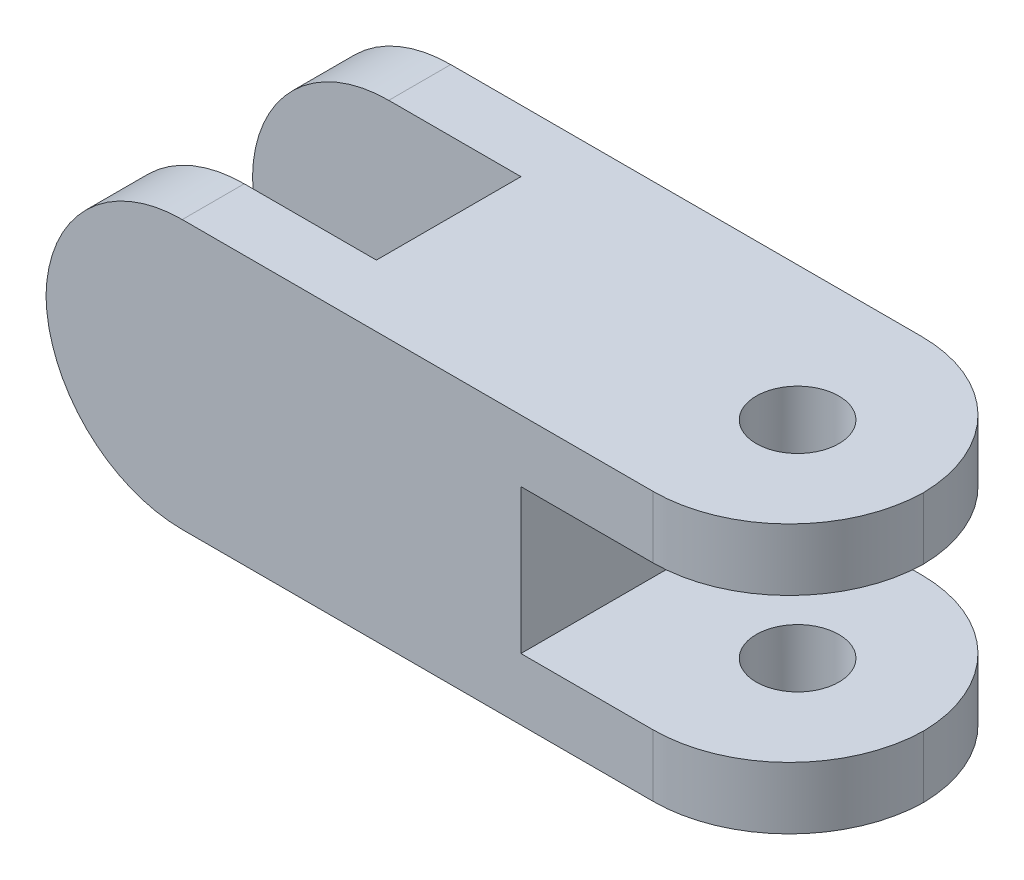
SolidWorks part; units mm, degrees
ref_plane "Plano frontal" through (0, 0, 0) normal (0, 0, 1) x (1, 0, 0)
ref_plane "Plano superior" through (0, 0, 0) normal (0, 1, 0) x (1, 0, 0)
ref_plane "Plano direito" through (0, 0, 0) normal (1, 0, 0) x (0, 0, -1)
sketch "Esboço1" plane through (0, 0, 0) normal (0, 1, 0) x (1, 0, 0)
  line L1 (-90, 32.5) -> (90, 32.5)
  line L2 (-90, 32.5) -> (-90, -32.5)
  line L3 (-90, -32.5) -> (90, -32.5)
  line L4 (90, 32.5) -> (90, -32.5)
  line L5 (-90, 32.5) -> (90, -32.5) construction
  line L6 (-90, -32.5) -> (90, 32.5) construction
  point P0 (0, 0)
  point P6 (0, 0)
  dimension "D1" = 180
  dimension "D2" = 65
extrude "Ressalto-extrusão3" add sketch "Esboço1" along normal mid plane 65
fillet "Filete6" radius 33 2 edges at (90, 0, -32.5) (90, 0, 32.5)
sketch "Esboço5" plane through (0, 0, 32.5) normal (0, 0, 1) x (1, 0, 0)
  line L0 (89.9962, 32.5) -> (89.9962, -32.5) construction
  line L1 (89.9962, 17.5) -> (24.9962, 17.5)
  line L2 (89.9962, 17.5) -> (89.9962, -17.5)
  line L3 (89.9962, -17.5) -> (24.9962, -17.5)
  line L4 (24.9962, 17.5) -> (24.9962, -17.5)
  line L5 (89.9962, 32.5) -> (57, 32.5) construction
  line L6 (57, -32.5) -> (89.9962, -32.5) construction
  dimension "D1" = 15
  dimension "D2" = 15
  dimension "D3" = 65
extrude "Corte-extrusão2" cut sketch "Esboço5" against normal through all both and the other way through all contours L2 L1 L4 L3
fillet "Filete7" radius 33 2 edges at (-90, -32.5, 0) (-90, 32.5, 0)
sketch "Esboço8" plane through (0, 32.5, 0) normal (0, 1, 0) x (1, 0, 0)
  line L0 (-89.9962, -32.5) -> (-89.9962, 32.5) construction
  line L1 (-89.9962, 17.5) -> (-24.9962, 17.5)
  line L2 (-89.9962, 17.5) -> (-89.9962, -17.5)
  line L3 (-89.9962, -17.5) -> (-24.9962, -17.5)
  line L4 (-24.9962, 17.5) -> (-24.9962, -17.5)
  line L5 (-57, 32.5) -> (-89.9962, 32.5) construction
  line L6 (-89.9962, -32.5) -> (-57, -32.5) construction
  dimension "D1" = 15
  dimension "D2" = 15
  dimension "D3" = 65
extrude "Corte-extrusão3" cut sketch "Esboço8" against normal through all both contours L2 L1 L4 L3
sketch "Esboço11" plane through (0, 32.5, 0) normal (0, 1, 0) x (1, 0, 0)
  circle A0 centre (59.4857, 0) radius 10
  point P2 (59.4857, 0)
  point P3 (0, 0)
  point P5 (64.7107, 0)
  dimension "D1" = 20
extrude "Corte-extrusão4" cut sketch "Esboço11" against normal through all both and the other way through all
